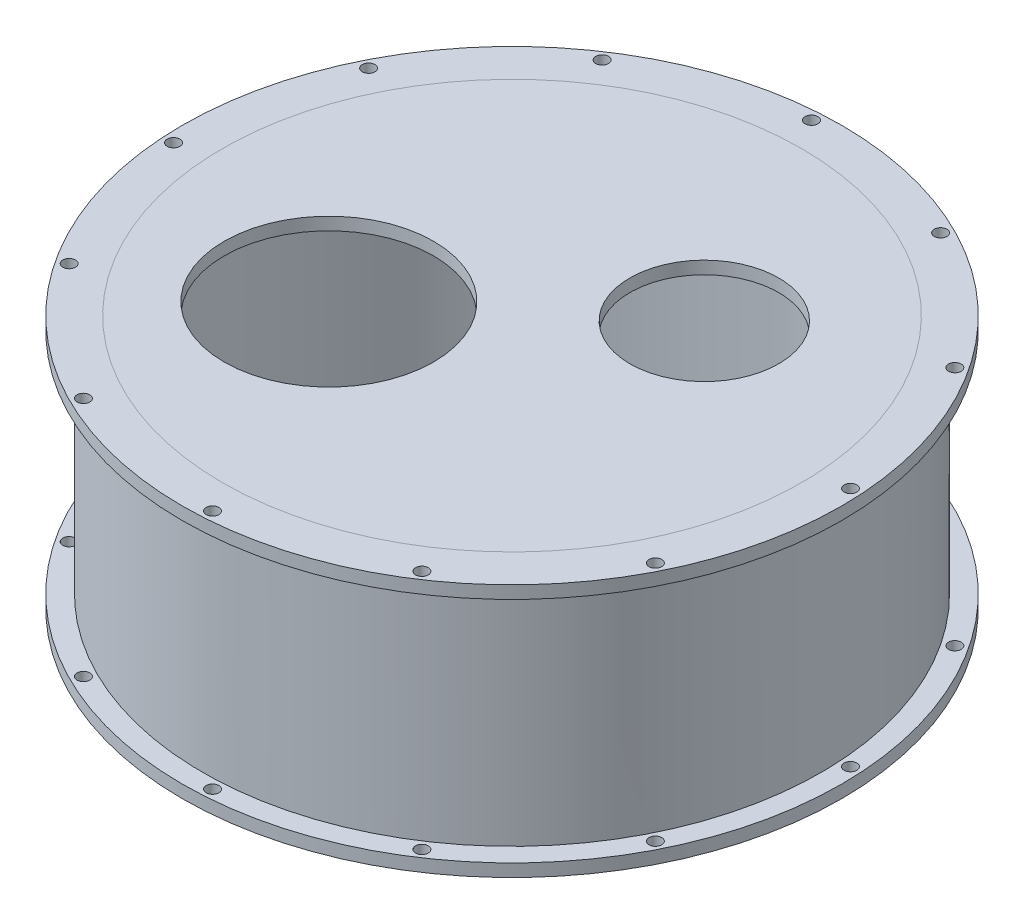
SolidWorks part; units mm, degrees
ref_plane "Front Plane" through (0, 0, 0) normal (0, 0, 1) x (1, 0, 0)
ref_plane "Top Plane" through (0, 0, 0) normal (0, 1, 0) x (1, 0, 0)
ref_plane "Right Plane" through (0, 0, 0) normal (1, 0, 0) x (0, 0, -1)
sketch "Sketch1" plane through (0, 0, 0) normal (0, 1, 0) x (1, 0, 0)
  circle A0 centre (0, 0) radius 155
  circle A3 centre (0, 0) radius 145
  dimension "D1" = 310
  dimension "D2" = 290
extrude "Boss-Extrude1" add sketch "Sketch1" along normal blind 63.5
ref_plane "Plane1" through (0, 0, 0) normal (0, -1, 0) x (-1, 0, 0)
sketch "Sketch2" plane through (0, 0, 0) normal (0, -1, 0) x (1, 0, 0)
  circle A0 centre (0, 0) radius 155 construction
  circle A1 centre (0, 0) radius 155
  circle A2 centre (0, 0) radius 165.16
  dimension "D1" = 10.16
extrude "Boss-Extrude2" add sketch "Sketch2" against normal blind 6.35
ref_plane "Plane2" through (0, 63.5, 0) normal (0, 1, 0) x (1, 0, 0)
mirror "Mirror2" about plane through (0, 63.5, 0) normal (0, 1, 0) of "Boss-Extrude2", "Boss-Extrude1"
sketch "Sketch3" plane through (0, 127, 0) normal (0, 1, 0) x (1, 0, 0)
  circle A0 centre (0, 0) radius 145 construction
  circle A1 centre (0, 0) radius 145
  circle A2 centre (50.4368, 45.8953) radius 37.2774
  circle A3 centre (-51.9358, -39.8005) radius 52.4437
extrude "Boss-Extrude4" add sketch "Sketch3" against normal blind 6.35 separate body contours A1 | A3 | A2
sketch "Sketch7" plane through (0, 127, 0) normal (0, 1, 0) x (1, 0, 0)
  line L0 (0, 0) -> (10.077, -164.8523) construction
  line L1 (10.077, -164.8523) -> (9.4571, -154.7112) construction
  circle A0 centre (0, 0) radius 155 construction
  circle A1 centre (0, 0) radius 165.16
  circle A2 centre (0, 0) radius 165.16
  circle A3 centre (0, 0) radius 155
  point P6 (9.7671, -159.7818)
  dimension "D1" = 0
hole_wizard "1/4 (0.25) Diameter Hole2" positions "3DSketch1" profile "Sketch10" hole size "1/4" standard "ANSI Inch"
sketch3d "3DSketch1"
  point P0 (9.7671, 127, 159.7818)
sketch "Sketch10" plane through (9.7671, 127, 159.7818) normal (1, 0, 0) x (0, 0, 1)
  line L0 (0, 0) -> (0, 8.2577)
  line L1 (0, 8.2577) -> (3.175, 6.35)
  line L2 (3.175, 6.35) -> (3.175, 0)
  line L5 (3.175, 0) -> (0, 0)
  line L10 (0, 8.2577) -> (-3.175, 6.35) construction
  line L11 (0, -6.35) -> (0, 107.95) construction
  dimension "Hole Dia." = 6.35
  dimension "Hole Depth" = 6.35
  dimension "Drill Angle" = 118
mirror "Mirror6" about plane through (0, 63.5, 0) normal (0, 1, 0) of "1/4 (0.25) Diameter Hole2"
pattern_circular "CirPattern2" count 12 over 360 about axis through (0, 0, 0) along (0, 1, 0) of "1/4 (0.25) Diameter Hole2", "Mirror6"
ref_point "Point1"
ref_point "Point2"
ref_plane "Plane3" through (-1.8087, 0, -2.1607) normal (0.6419, 0, 0.7668) x (0.7668, 0, -0.6419)
